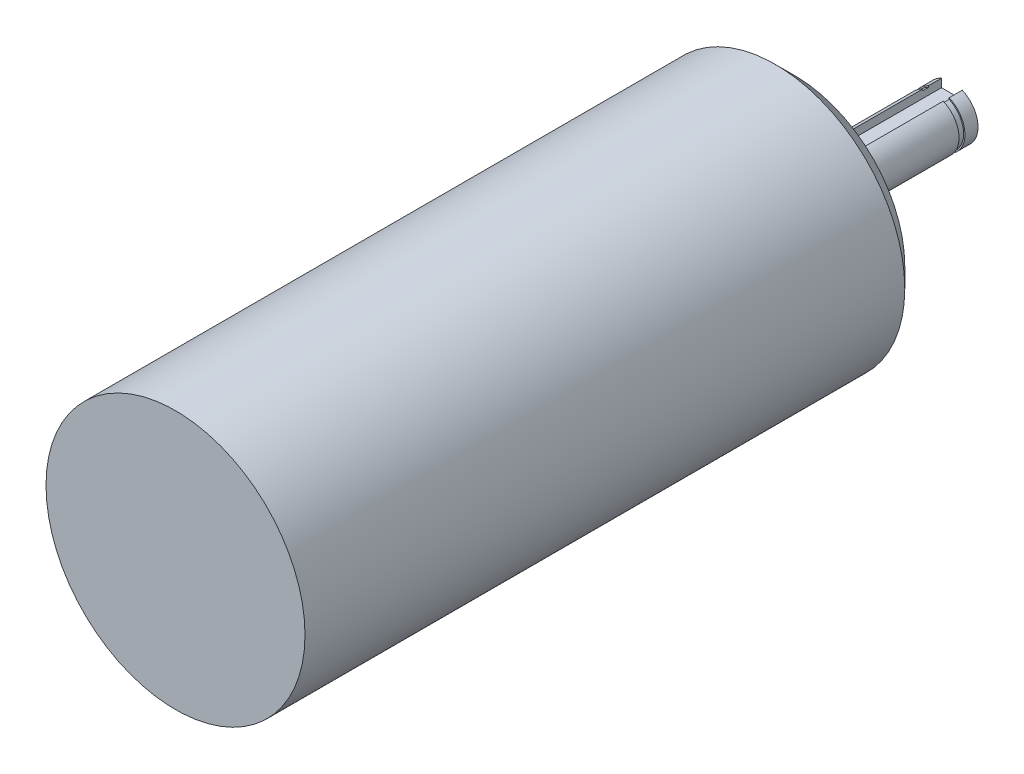
SolidWorks part; units mm, degrees
ref_plane "Front Plane" through (0, 0, 0) normal (0, 0, 1) x (1, 0, 0)
ref_plane "Top Plane" through (0, 0, 0) normal (0, 1, 0) x (1, 0, 0)
ref_plane "Right Plane" through (0, 0, 0) normal (1, 0, 0) x (0, 0, -1)
sketch "Sketch1" plane through (0, 0, 0) normal (0, 0, 1) x (1, 0, 0)
  circle A0 centre (0, 0) radius 19.8
  dimension "D1" = 39.6
extrude "Boss-Extrude1" add sketch "Sketch1" along normal blind 94.7
sketch "face mounting holes" plane through (0, 0, 0) normal (0, 0, -1) x (-1, 0, 0)
  point P0 (0, 12.5)
  point P4 (12.5, 0)
  point P5 (0, -12.5)
  point P6 (-12.5, 0)
  point P7 (0, 0)
  dimension "D2" = 25
  dimension "D1" = 4
hole_wizard "M4x0.7 Tapped Hole1" positions "Sketch3" profile "Sketch5" tap size "M4x0.7" standard "ANSI Metric"
sketch "Sketch3" plane through (0, 0, 0) normal (0, 0, -1) x (-1, 0, 0)
  point P0 (0, 12.5)
  point P3 (-12.5, 0)
  point P6 (0, -12.5)
  point P9 (12.5, 0)
sketch "Sketch5" plane through (0, 12.5, 0) normal (1, 0, 0) x (0, 1, 0)
  line L0 (0, 0) -> (0, 4.9914)
  line L1 (0, 4.9914) -> (1.65, 4)
  line L2 (1.65, 4) -> (1.65, 0.375)
  line L3 (1.65, 0.375) -> (2.025, 0)
  line L5 (2.025, 0) -> (0, 0)
  line L6 (-1.65, 0.375) -> (-2.025, 0) construction
  line L10 (0, 4.9914) -> (-1.65, 4) construction
  line L11 (0, -6.35) -> (0, 107.95) construction
  dimension "Tap Drill Dia." = 3.3
  dimension "Tap Drill Depth" = 4
  dimension "Near C'Sink Dia." = 4.05
  dimension "Near C'Sink Angle" = 90
  dimension "Drill Angle" = 118
cosmetic thread "Hole Thread1" parameters "D1"=4, "D2"=4
cosmetic thread "Hole Thread2" parameters "D1"=4, "D2"=4
cosmetic thread "Hole Thread3" parameters "D1"=4, "D2"=4
cosmetic thread "Hole Thread4" parameters "D1"=4, "D2"=4
sketch "Sketch6" plane through (0, 0, 0) normal (0, 0, -1) x (-1, 0, 0)
  circle A0 centre (0, 0) radius 4
  dimension "D1" = 8
extrude "Boss-Extrude2" add sketch "Sketch6" along normal blind 24
chamfer "Chamfer1" distance 3 angle 45 1 edges at (19.8, 0, 0)
sketch "Sketch7" plane through (0, 0, -24) normal (0, 0, -1) x (-1, 0, 0)
  line L1 (-1.5875, 2.4125) -> (1.5875, 2.4125)
  line L2 (-1.5875, 2.4125) -> (-1.5875, 5.5875)
  line L3 (-1.5875, 5.5875) -> (1.5875, 5.5875)
  line L4 (1.5875, 2.4125) -> (1.5875, 5.5875)
  line L5 (-1.5875, 2.4125) -> (1.5875, 5.5875) construction
  line L6 (-1.5875, 5.5875) -> (1.5875, 2.4125) construction
  circle A0 centre (0, 0) radius 4 construction
  point P0 (0, 4)
  point P7 (0, 0)
  dimension "D1" = 3.175
  dimension "D2" = 3.175
extrude "Cut-Extrude1" cut sketch "Sketch7" against normal blind 16
ref_plane "Plane1" through (0, 0, -22) normal (0, 0, -1) x (-1, 0, 0)
sketch "Sketch8" plane through (0, 0, -22) normal (0, 0, -1) x (-1, 0, 0)
  circle A0 centre (0, 0) radius 3.8
  circle A1 centre (0, 0) radius 4
  arc A2 (-1.5875, 3.6715) -> (1.5875, 3.6715) centre (0, 0) ccw construction
  dimension "D1" = 7.6
extrude "Cut-Extrude2" cut sketch "Sketch8" against normal blind 0.9
equation "\"D1@Sketch7\"=0.125in"
equation "\"D2@Sketch7\"=0.125in"
